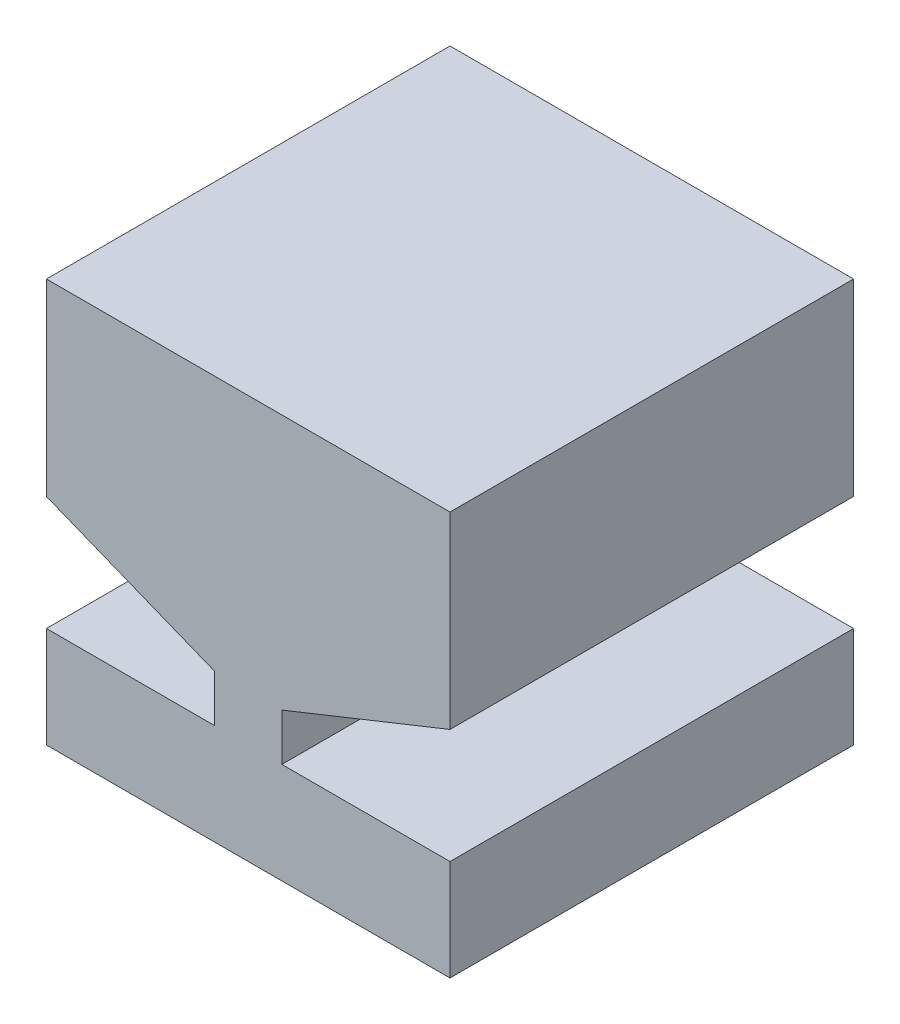
SolidWorks part; units mm, degrees
ref_plane "Plan de face" through (0, 0, 0) normal (0, 0, 1) x (1, 0, 0)
ref_plane "Plan de dessus" through (0, 0, 0) normal (0, 1, 0) x (1, 0, 0)
ref_plane "Plan de droite" through (0, 0, 0) normal (1, 0, 0) x (0, 0, -1)
sketch "Esquisse1" plane through (0, 0, 0) normal (0, 0, 1) x (1, 0, 0)
  line L0 (0, 0) -> (60, 0)
  line L1 (0, 0) -> (60, 0) construction
  line L2 (0, 0) -> (0, 60) construction
  line L3 (0, 60) -> (60, 60) construction
  line L4 (60, 0) -> (60, 60) construction
  line L5 (60, 0) -> (60, 15)
  line L6 (60, 15) -> (35, 15)
  line L7 (35, 15) -> (35, 22)
  line L8 (35, 22) -> (60, 32)
  line L9 (60, 32) -> (60, 60)
  line L10 (60, 60) -> (0, 60)
  line L11 (0, 60) -> (0, 32)
  line L12 (0, 32) -> (25, 22)
  line L13 (25, 22) -> (25, 15)
  line L14 (25, 15) -> (0, 15)
  line L15 (0, 15) -> (0, 0)
  dimension "D1" = 60
  dimension "D2" = 60
  dimension "D3" = 32
  dimension "D4" = 32
  dimension "D5" = 10
  dimension "D6" = 10
  dimension "D7" = 7
  dimension "D8" = 7
  dimension "D9" = 25
  dimension "D10" = 25
extrude "Boss.-Extru.1" add sketch "Esquisse1" along normal blind 60
